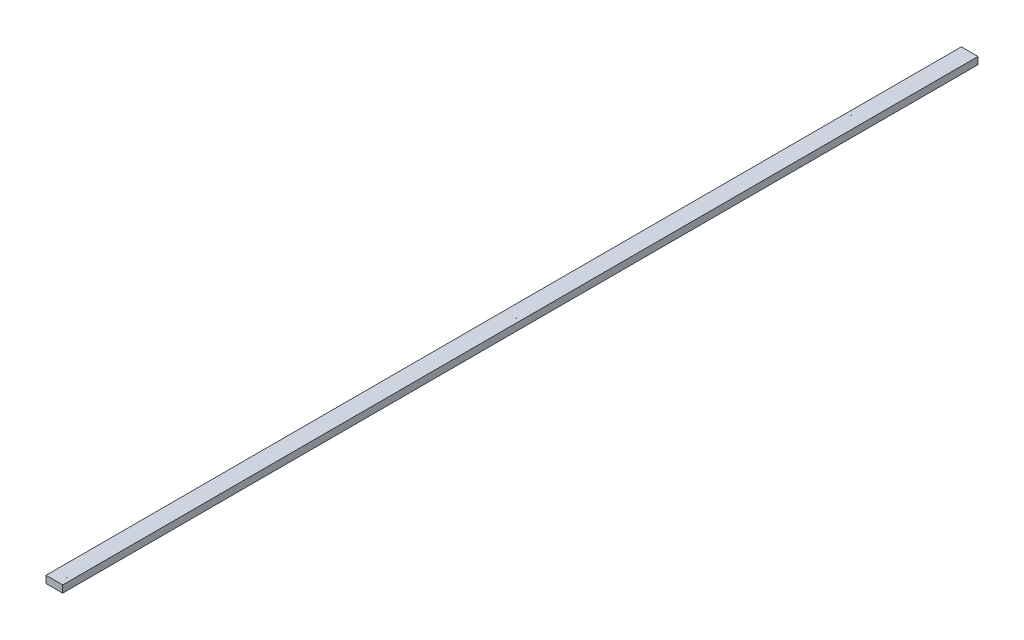
SolidWorks part; units mm, degrees
material "Pine"
ref_plane "Front Plane" through (0, 0, 0) normal (0, 0, 1) x (1, 0, 0)
ref_plane "Top Plane" through (0, 0, 0) normal (0, 1, 0) x (1, 0, 0)
ref_plane "Right Plane" through (0, 0, 0) normal (1, 0, 0) x (0, 0, -1)
sketch "Sketch1" plane through (0, 0, 0) normal (0, 0, 1) x (1, 0, 0)
  line L1 (0, 0) -> (88.9, 0)
  line L2 (0, 0) -> (0, 38.1)
  line L3 (0, 38.1) -> (88.9, 38.1)
  line L4 (88.9, 0) -> (88.9, 38.1)
  dimension "D1" = 88.9
  dimension "D2" = 38.1
extrude "Boss-Extrude1" add sketch "Sketch1" along normal blind 4876.8
sketch "Sketch3" plane through (0, 38.1, 0) normal (0, 1, 0) x (1, 0, 0)
  line L0 (88.9, -609.6) -> (44.45, -609.6) construction
  line L1 (66.675, -4832.35) -> (22.225, -4832.35) construction
  line L2 (44.45, -609.6) -> (0, -609.6) construction
  line L3 (88.9, -2438.4) -> (44.45, -2438.4) construction
  line L4 (44.45, -4832.35) -> (44.45, -4876.8) construction
  line L5 (88.9, -4876.8) -> (0, -4876.8) construction
  line L6 (88.9, -4876.8) -> (88.9, 0) construction
  line L7 (44.45, -2438.4) -> (0, -2438.4) construction
  line L8 (0, -4876.8) -> (0, 0) construction
  line L9 (88.9, 0) -> (0, 0) construction
  circle A0 centre (66.675, -2438.4) radius 0.8763
  circle A1 centre (22.225, -2438.4) radius 0.8763
  circle A2 centre (66.675, -609.6) radius 0.8763
  circle A3 centre (22.225, -609.6) radius 0.8763
  circle A4 centre (22.225, -4832.35) radius 0.8763
  circle A5 centre (66.675, -4832.35) radius 0.8763
  dimension "D2" = 1.7526
  dimension "D4" = 44.45
  dimension "D3" = 1.7526
  dimension "D1" = 609.6
  dimension "D5" = 44.45
extrude "Cut-Extrude2" cut sketch "Sketch3" against normal up to surface (38.1 mm away) up to face at (44.45, 0, 2438.4)
equation "\"length\"= 1219.2 * 4"
equation "\"D1@Boss-Extrude1\"=\"length\""
